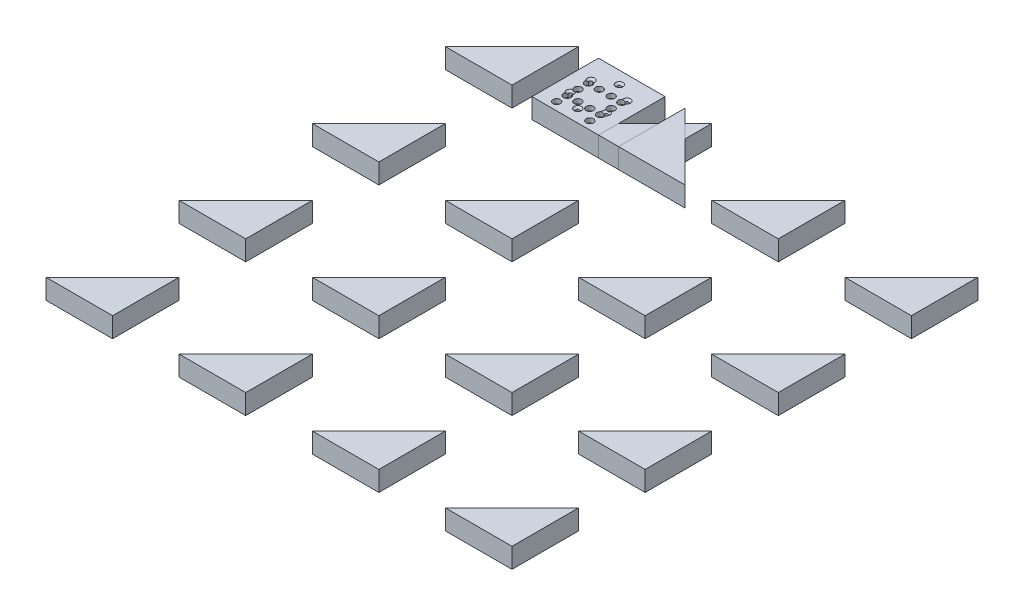
SolidWorks part; units mm, degrees
ref_plane "前视基准面" through (0, 0, 0) normal (0, 0, 1) x (1, 0, 0)
ref_plane "上视基准面" through (0, 0, 0) normal (0, 1, 0) x (1, 0, 0)
ref_plane "右视基准面" through (0, 0, 0) normal (1, 0, 0) x (0, 0, -1)
sketch "草图1" plane through (0, 0, 0) normal (0, 1, 0) x (1, 0, 0)
  line L0 (80, -50) -> (180, -50)
  line L1 (-50, 50) -> (50, 50)
  line L2 (-50, 50) -> (-50, -50)
  line L3 (-50, -50) -> (50, -50)
  line L4 (50, 50) -> (50, -50)
  line L5 (-50, 50) -> (50, -50) construction
  line L6 (-50, -50) -> (50, 50) construction
  line L7 (180, -50) -> (80, 50)
  line L8 (80, 50) -> (80, -50)
  point P0 (0, 0)
  point P8 (0, 0)
  dimension "D1" = 100
  dimension "D2" = 100
  dimension "D3" = 30
extrude "凸台-拉伸1" add sketch "草图1" along normal blind 30
hole_wizard "打孔尺寸(%根据)内六角圆柱头螺钉的类型2" positions "草图6" profile "草图7" counterbore size "M6" standard "GB" end condition through all
sketch "草图6" plane through (0, 30, 0) normal (0, 1, 0) x (1, 0, 0)
  line L0 (-50, 50) -> (-50, -50) construction
  line L1 (50, 50) -> (-50, 50) construction
  point P0 (-25, 10)
  point P24 (0, 0)
  dimension "D1" = 25
  dimension "D2" = 40
sketch "草图7" plane through (-25, 30, -10) normal (1, 0, 0) x (0, 0, 1)
  line L0 (0, 0) -> (0, 30)
  line L1 (0, 30) -> (3.5, 30)
  line L3 (3.5, 30) -> (3.5, 6.8)
  line L4 (5.5, 6.8) -> (3.5, 6.8)
  line L5 (5.5, 6.8) -> (5.5, 0.021)
  line L6 (5.5, 0.021) -> (5.525, 0)
  line L7 (5.525, 0) -> (0, 0)
  line L8 (-5.5, 0.021) -> (-5.525, 0) construction
  line L11 (0, -6.35) -> (0, 107.95) construction
  dimension "通孔孔直径" = 7
  dimension "通孔孔深度" = 30
  dimension "柱形沉头孔直径" = 11
  dimension "柱形沉头孔深度" = 6.8
  dimension "近端锥形沉头孔直径" = 11.05
  dimension "近端锥形沉头孔角度" = 100
hole_wizard "M6 螺纹孔1" positions "草图8" profile "草图9" tap size "M6" standard "GB" end condition through all
sketch "草图8" plane through (0, 30, 0) normal (0, 1, 0) x (1, 0, 0)
  point P0 (0, 31.2085)
  point P5 (0, 0)
sketch "草图9" plane through (0, 30, -31.2085) normal (1, 0, 0) x (0, 0, 1)
  line L0 (0, 0) -> (0, 30)
  line L1 (0, 30) -> (2.5, 30)
  line L2 (2.5, 30) -> (2.5, 2.5383)
  line L3 (2.5, 2.5383) -> (5.525, 0)
  line L5 (5.525, 0) -> (0, 0)
  line L6 (-2.5, 2.5383) -> (-5.525, 0) construction
  line L11 (0, -6.35) -> (0, 107.95) construction
  dimension "通孔螺纹孔钻头直径" = 5
  dimension "通孔螺纹孔钻头深度" = 30
  dimension "近端锥形沉头孔直径" = 11.05
  dimension "近端锥形沉头孔角度" = 100
cosmetic thread "孔螺蚊线2" parameters "D2"=6
pattern_linear "阵列(线性)1" count 4 spacing 16 along (1, 0, 0) count 4 spacing 16 along (0, 0, 1) skipping (1, 1), (1, 3), (2, 0), (2, 1), (2, 2), (2, 3), (3, 0), (3, 1), (3, 2), (3, 3) of "打孔尺寸(%根据)内六角圆柱头螺钉的类型2"
ref_axis "基准轴1" through (0, 0, 0) along (0, 1, 0)
pattern_circular "阵列(圆周)1" count 6 over 360 about axis through (0, 0, 0) along (0, 1, 0) of "M6 螺纹孔1"
cosmetic thread "孔螺蚊线3" parameters "D2"=6
cosmetic thread "孔螺蚊线4" parameters "D2"=6
cosmetic thread "孔螺蚊线5" parameters "D2"=6
cosmetic thread "孔螺蚊线6" parameters "D2"=6
cosmetic thread "孔螺蚊线7" parameters "D2"=6
mirror "镜向4" about plane through (0, 0, 0) normal (1, 0, 0) of "阵列(线性)1"
mirror "镜向6" about plane through (0, 0, 0) normal (1, 0, 0) of bodies 107
pattern_linear "阵列(线性)2" count 4 spacing 200 along (1, 0, 0) count 4 spacing 200 along (0, 0, 1) of bodies 114
